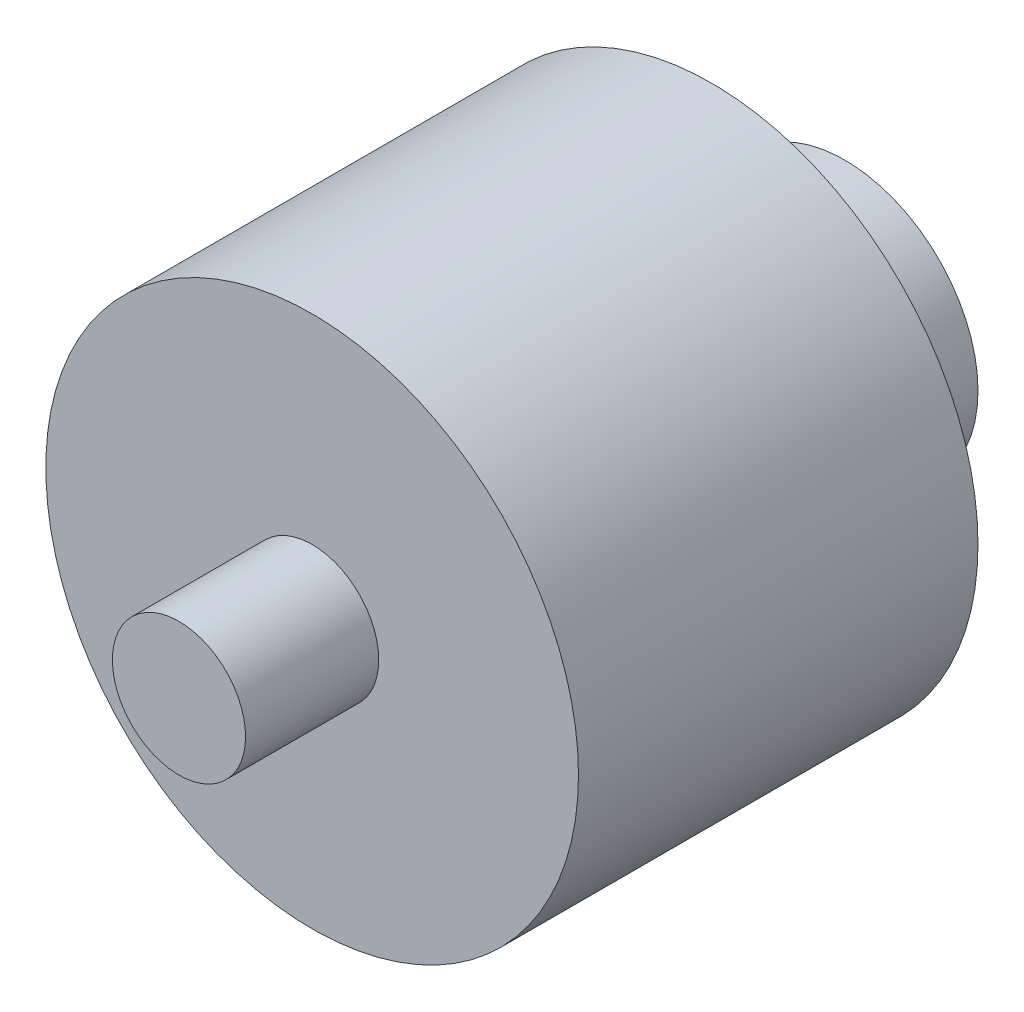
SolidWorks part; units mm, degrees
ref_plane "Front Plane" through (0, 0, 0) normal (0, 0, 1) x (1, 0, 0)
ref_plane "Top Plane" through (0, 0, 0) normal (0, 1, 0) x (1, 0, 0)
ref_plane "Right Plane" through (0, 0, 0) normal (1, 0, 0) x (0, 0, -1)
sketch "Sketch1" plane through (0, 0, 0) normal (0, 0, 1) x (1, 0, 0)
  circle A0 centre (0, 0) radius 6
  circle A1 centre (0, 0) radius 3
  dimension "D1" = 12
  dimension "D2" = 6
extrude "Boss-Extrude1" add sketch "Sketch1" along normal blind 6
sketch "Sketch2" plane through (0, 0, 6) normal (0, 0, 1) x (1, 0, 0)
  circle A0 centre (0, 0) radius 12
  dimension "D1" = 24
extrude "Boss-Extrude3" add sketch "Sketch2" along normal blind 18
sketch "Sketch3" plane through (0, 0, 24) normal (0, 0, 1) x (1, 0, 0)
  circle A0 centre (0, 0) radius 3
  dimension "D1" = 6
extrude "Boss-Extrude4" add sketch "Sketch3" along normal blind 6
